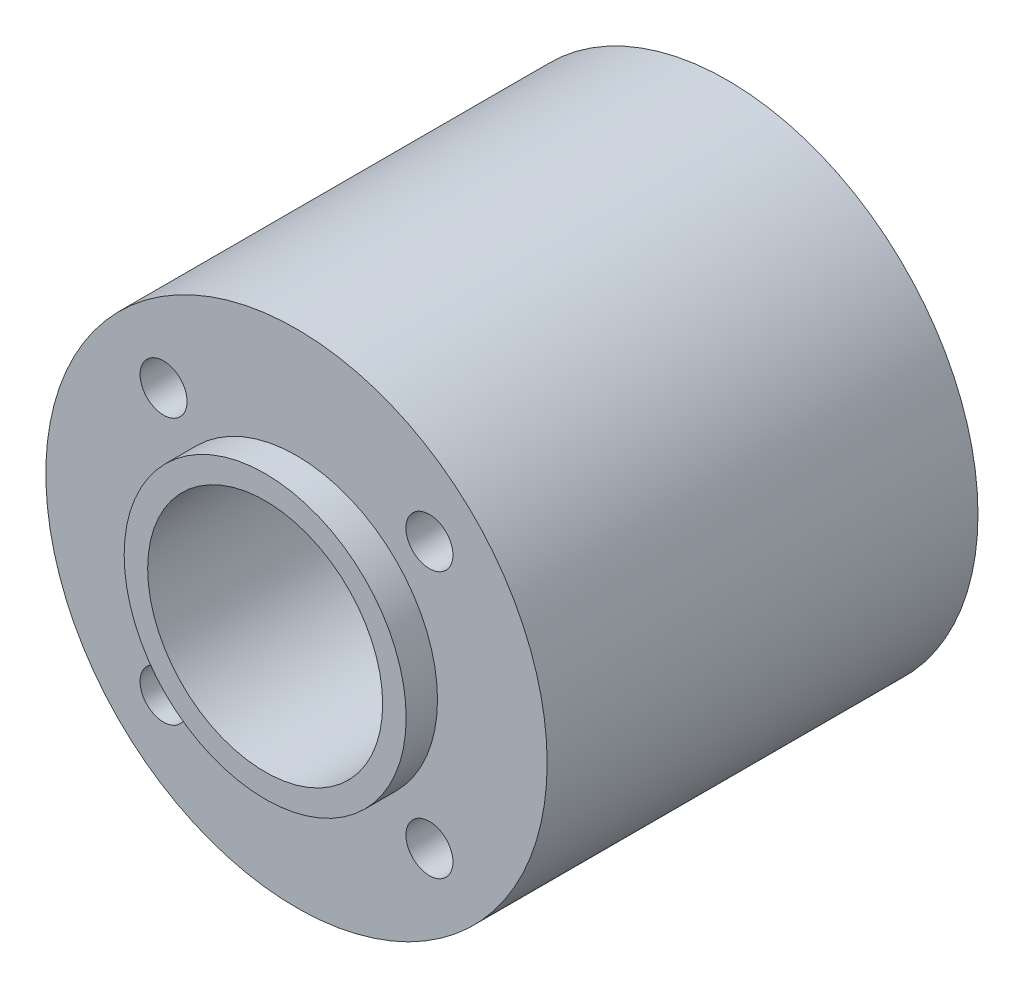
SolidWorks part; units mm, degrees
ref_plane "Front Plane" through (0, 0, 0) normal (0, 0, 1) x (1, 0, 0)
ref_plane "Top Plane" through (0, 0, 0) normal (0, 1, 0) x (1, 0, 0)
ref_plane "Right Plane" through (0, 0, 0) normal (1, 0, 0) x (0, 0, -1)
sketch "Sketch1" plane through (0, 0, 0) normal (0, 0, 1) x (1, 0, 0)
  circle A0 centre (0, 0) radius 16
  circle A1 centre (0, 0) radius 9
  circle A2 centre (0, 0) radius 7.5
  dimension "D1" = 32
  dimension "D2" = 18
  dimension "D3" = 15
extrude "Boss-Extrude1" add sketch "Sketch1" against normal blind 27.5 contours A0 A1 | A1 A2 region at (-15.5475, 0, 0) region at (-8.7454, 0, 0)
extrude "Boss-Extrude2" add sketch "Sketch1<3>" along normal blind 2 contours A1 A2 region at (-8.7454, 0, 0)
sketch "Sketch1<3>" plane through (0, 0, 0) normal (0, 0, 1) x (1, 0, 0) same geometry as "Sketch1"
sketch "Sketch3" plane through (0, 0, 0) normal (0, 0, 1) x (1, 0, 0)
  line L0 (0, 12) -> (0, 0) construction
  line L1 (0, 0) -> (-8.4853, 8.4853) construction
  circle A0 centre (0, 0) radius 12 construction
  circle A1 centre (-8.4853, 8.4853) radius 1.5
  circle A2 centre (8.4853, 8.4853) radius 1.5
  circle A3 centre (8.4853, -8.4853) radius 1.5
  circle A4 centre (-8.4853, -8.4853) radius 1.5
  circle A5 centre (0, 0) radius 9 construction
  point P15 (0, 0)
  dimension "D2" = 24
  dimension "D3" = 3
  dimension "D1" = 45
  dimension "D4" = 4
extrude "Cut-Extrude1" cut sketch "Sketch3" against normal blind 47
extrude "Boss-Extrude5" add sketch "Sketch1<5>" against normal blind 2 from surface contours A1 A2 region at (-8.7454, 0, 0) starting at face at (-6.9853, -8.4853, -27.5)
sketch "Sketch1<5>" plane through (0, 0, 0) normal (0, 0, 1) x (1, 0, 0) same geometry as "Sketch1"
scale "Scale1" scale about centroid uniform scaling yes scale factor 1.667
